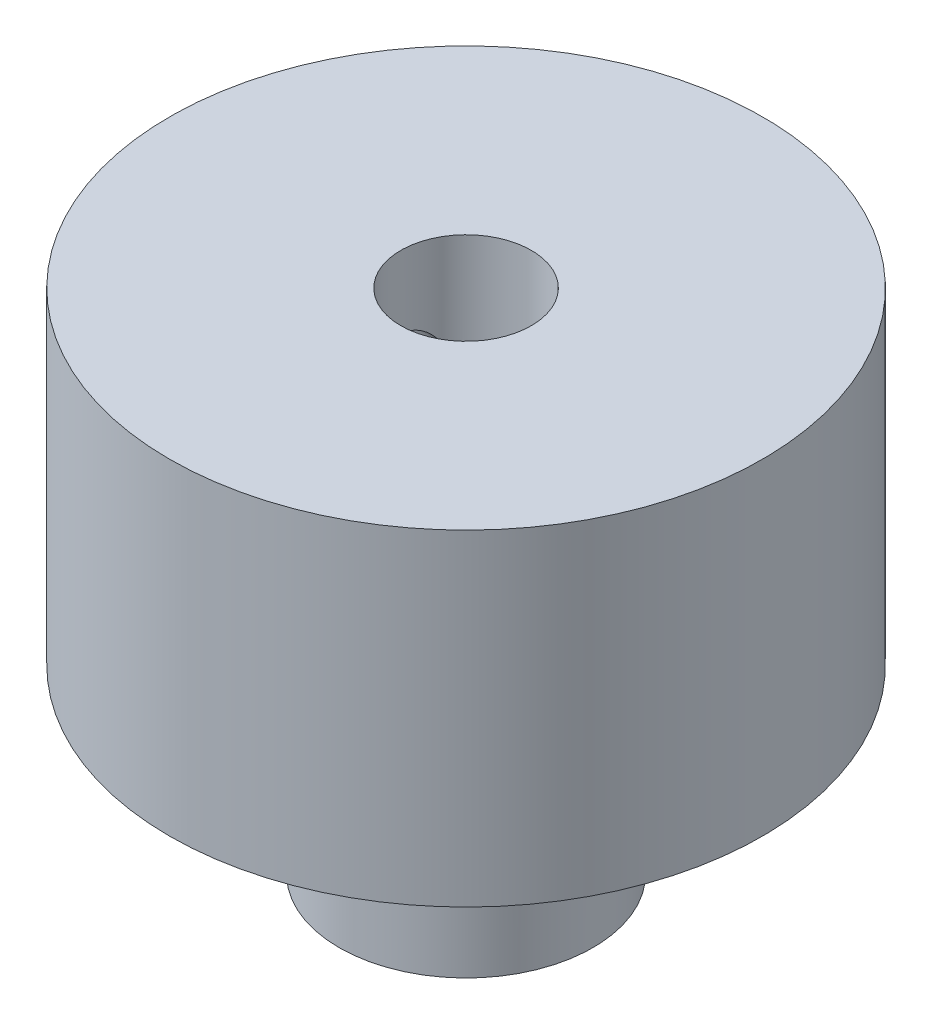
SolidWorks part; units mm, degrees
ref_plane "Front Plane" through (0, 0, 0) normal (0, 0, 1) x (1, 0, 0)
ref_plane "Top Plane" through (0, 0, 0) normal (0, 1, 0) x (1, 0, 0)
ref_plane "Right Plane" through (0, 0, 0) normal (1, 0, 0) x (0, 0, -1)
sketch "Sketch1" plane through (0, 0, 0) normal (0, 1, 0) x (1, 0, 0)
  circle A0 centre (0, 0) radius 1.8
  circle A1 centre (0, 0) radius 8.175
  circle A2 centre (0, 0) radius 8.175
  point P25 (0, 0)
extrude "Boss-Extrude1" add sketch "Sketch1" along normal blind 6 and the other way blind 3 contours A1 A0 region at (-7.9438, 0, 0)
extrude "Boss-Extrude2" add sketch "Sketch1<3>" against normal blind 3 separate body contours A2 A1 region at (-7.9438, 0, 0)
sketch "Sketch1<3>" plane through (0, 0, 0) normal (0, 1, 0) x (1, 0, 0) same geometry as "Sketch1"
sketch "Sketch2" plane through (0, 0, 0) normal (1, 0, 0) x (0, 0, -1)
  line L0 (0, 0) -> (0, 2)
  line L1 (0, 4) -> (0, 6)
  circle A0 centre (0, 3) radius 1
  dimension "D1" = 2
extrude "Cut-Extrude1" cut sketch "Sketch2" against normal blind 15 contours A0
sketch "Sketch3" plane through (0, -3, 0) normal (0, -1, 0) x (1, 0, 0)
  circle A0 centre (0, 9.6613) radius 0.75
  circle A2 centre (9.1884, 2.9855) radius 0.75
  circle A3 centre (5.6787, -7.8161) radius 0.75
  circle A4 centre (-5.6787, -7.8161) radius 0.75
  circle A5 centre (-9.1884, 2.9855) radius 0.75
  point P14 (0, 0)
  dimension "D1" = 5
sketch "Sketch4" plane through (0, -3, 0) normal (0, -1, 0) x (1, 0, 0)
  circle A0 centre (0, 0) radius 3.5
extrude "Boss-Extrude3" add sketch "Sketch4" along normal blind 5 contours A0
extrude "Cut-Extrude2" cut sketch "Sketch1<7>" against normal blind 13 contours A0
sketch "Sketch1<7>" plane through (0, 0, 0) normal (0, 1, 0) x (1, 0, 0) same geometry as "Sketch1"
extrude "Cut-Extrude3" [suppressed] cut sketch "Sketch3" against normal blind 10
